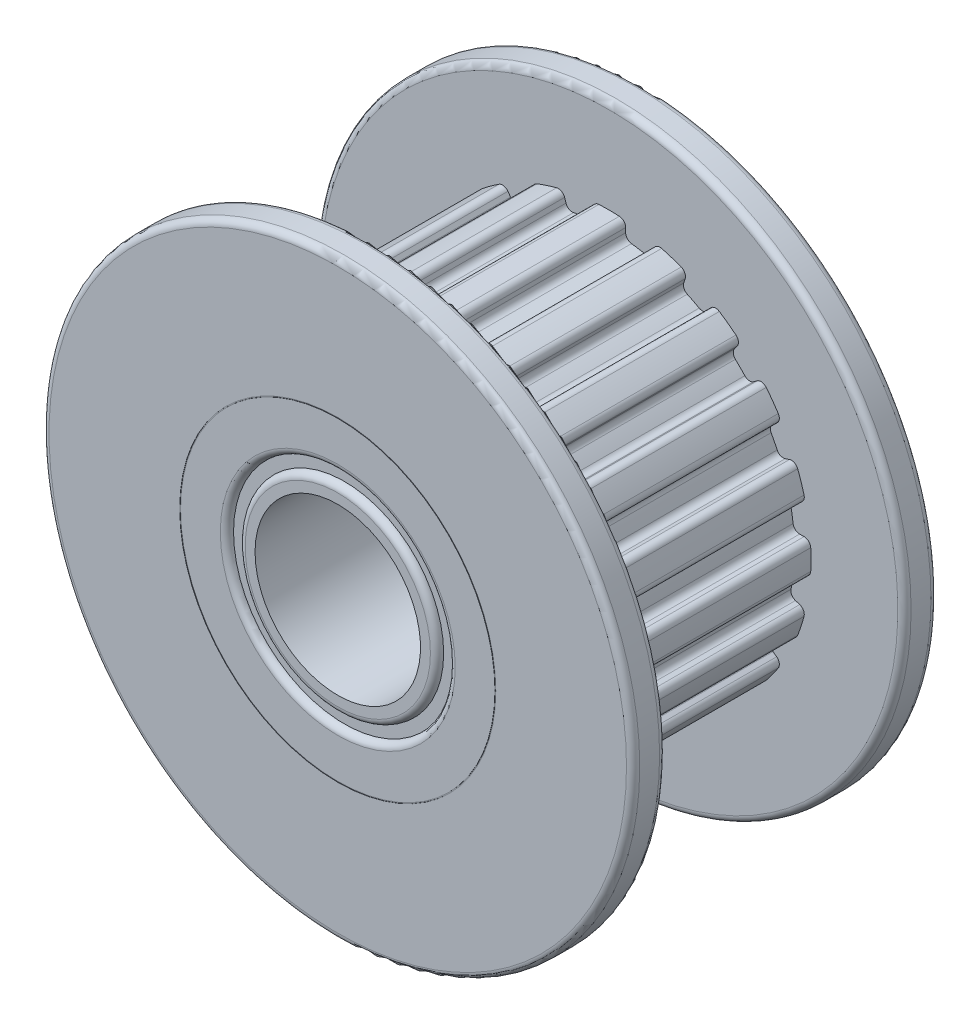
SolidWorks part; units mm, degrees
material "1060-H12 Válcovaný drát (SS)"
ref_plane "Front Plane" through (0, 0, 0) normal (0, 0, 1) x (1, 0, 0)
ref_plane "Top Plane" through (0, 0, 0) normal (0, 1, 0) x (1, 0, 0)
ref_plane "Right Plane" through (0, 0, 0) normal (1, 0, 0) x (0, 0, -1)
sketch "Skica1" plane through (0, 0, 0) normal (0, 0, 1) x (1, 0, 0)
  line L0 (0, 0) -> (0, 6.1) construction
  line L1 (0, 6.1) -> (-0.5, 6.0795) construction
  line L2 (0, 6.1) -> (0.5, 6.0795) construction
  line L3 (-0.5, 6.0795) -> (-0.5, 5.5776)
  line L4 (-0.5, 5.5776) -> (-1.2481, 5.4592) construction
  line L5 (0.5, 6.0795) -> (0.5, 5.5776)
  line L6 (1.4031, 5.9364) -> (1.2481, 5.4592)
  line L7 (2.3542, 5.6274) -> (2.1991, 5.1501)
  line L8 (3.1689, 5.2123) -> (2.8739, 4.8063)
  line L9 (3.9779, 4.6245) -> (3.683, 4.2185)
  line L10 (4.6245, 3.9779) -> (4.2185, 3.683)
  line L11 (5.2123, 3.1689) -> (4.8063, 2.8739)
  line L12 (5.6274, 2.3542) -> (5.1501, 2.1991)
  line L13 (5.9364, 1.4031) -> (5.4592, 1.2481)
  line L14 (6.0795, 0.5) -> (5.5776, 0.5)
  line L15 (6.0795, -0.5) -> (5.5776, -0.5)
  line L16 (5.9364, -1.4031) -> (5.4592, -1.2481)
  line L17 (5.6274, -2.3542) -> (5.1501, -2.1991)
  line L18 (5.2123, -3.1689) -> (4.8063, -2.8739)
  line L19 (4.6245, -3.9779) -> (4.2185, -3.683)
  line L20 (3.9779, -4.6245) -> (3.683, -4.2185)
  line L21 (3.1689, -5.2123) -> (2.8739, -4.8063)
  line L22 (2.3542, -5.6274) -> (2.1991, -5.1501)
  line L23 (1.4031, -5.9364) -> (1.2481, -5.4592)
  line L24 (0.5, -6.0795) -> (0.5, -5.5776)
  line L25 (-0.5, -6.0795) -> (-0.5, -5.5776)
  line L26 (-1.4031, -5.9364) -> (-1.2481, -5.4592)
  line L27 (-2.3542, -5.6274) -> (-2.1991, -5.1501)
  line L28 (-3.1689, -5.2123) -> (-2.8739, -4.8063)
  line L29 (-3.9779, -4.6245) -> (-3.683, -4.2185)
  line L30 (-4.6245, -3.9779) -> (-4.2185, -3.683)
  line L31 (-5.2123, -3.1689) -> (-4.8063, -2.8739)
  line L32 (-5.6274, -2.3542) -> (-5.1501, -2.1991)
  line L33 (-5.9364, -1.4031) -> (-5.4592, -1.2481)
  line L34 (-6.0795, -0.5) -> (-5.5776, -0.5)
  line L35 (-6.0795, 0.5) -> (-5.5776, 0.5)
  line L36 (-5.9364, 1.4031) -> (-5.4592, 1.2481)
  line L37 (-5.6274, 2.3542) -> (-5.1501, 2.1991)
  line L38 (-5.2123, 3.1689) -> (-4.8063, 2.8739)
  line L39 (-4.6245, 3.9779) -> (-4.2185, 3.683)
  line L40 (-3.9779, 4.6245) -> (-3.683, 4.2185)
  line L41 (-3.1689, 5.2123) -> (-2.8739, 4.8063)
  line L42 (-2.3542, 5.6274) -> (-2.1991, 5.1501)
  line L43 (-1.4031, 5.9364) -> (-1.2481, 5.4592)
  circle A0 centre (0, 0) radius 6.1 construction
  circle A1 centre (0, 0) radius 5.6 construction
  arc A2 (-1.2481, 5.4592) -> (-0.5, 5.5776) centre (0, 0) cw
  arc A3 (-0.5, 6.0795) -> (0.5, 6.0795) centre (0, 0) cw
  arc A4 (0.5, 5.5776) -> (1.2481, 5.4592) centre (0, 0) cw
  arc A5 (1.4031, 5.9364) -> (2.3542, 5.6274) centre (0, 0) cw
  arc A6 (2.1991, 5.1501) -> (2.8739, 4.8063) centre (0, 0) cw
  arc A7 (3.1689, 5.2123) -> (3.9779, 4.6245) centre (0, 0) cw
  arc A8 (3.683, 4.2185) -> (4.2185, 3.683) centre (0, 0) cw
  arc A9 (4.6245, 3.9779) -> (5.2123, 3.1689) centre (0, 0) cw
  arc A10 (4.8063, 2.8739) -> (5.1501, 2.1991) centre (0, 0) cw
  arc A11 (5.6274, 2.3542) -> (5.9364, 1.4031) centre (0, 0) cw
  arc A12 (5.4592, 1.2481) -> (5.5776, 0.5) centre (0, 0) cw
  arc A13 (6.0795, 0.5) -> (6.0795, -0.5) centre (0, 0) cw
  arc A14 (5.5776, -0.5) -> (5.4592, -1.2481) centre (0, 0) cw
  arc A15 (5.9364, -1.4031) -> (5.6274, -2.3542) centre (0, 0) cw
  arc A16 (5.1501, -2.1991) -> (4.8063, -2.8739) centre (0, 0) cw
  arc A17 (5.2123, -3.1689) -> (4.6245, -3.9779) centre (0, 0) cw
  arc A18 (4.2185, -3.683) -> (3.683, -4.2185) centre (0, 0) cw
  arc A19 (3.9779, -4.6245) -> (3.1689, -5.2123) centre (0, 0) cw
  arc A20 (2.8739, -4.8063) -> (2.1991, -5.1501) centre (0, 0) cw
  arc A21 (2.3542, -5.6274) -> (1.4031, -5.9364) centre (0, 0) cw
  arc A22 (1.2481, -5.4592) -> (0.5, -5.5776) centre (0, 0) cw
  arc A23 (0.5, -6.0795) -> (-0.5, -6.0795) centre (0, 0) cw
  arc A24 (-0.5, -5.5776) -> (-1.2481, -5.4592) centre (0, 0) cw
  arc A25 (-1.4031, -5.9364) -> (-2.3542, -5.6274) centre (0, 0) cw
  arc A26 (-2.1991, -5.1501) -> (-2.8739, -4.8063) centre (0, 0) cw
  arc A27 (-3.1689, -5.2123) -> (-3.9779, -4.6245) centre (0, 0) cw
  arc A28 (-3.683, -4.2185) -> (-4.2185, -3.683) centre (0, 0) cw
  arc A29 (-4.6245, -3.9779) -> (-5.2123, -3.1689) centre (0, 0) cw
  arc A30 (-4.8063, -2.8739) -> (-5.1501, -2.1991) centre (0, 0) cw
  arc A31 (-5.6274, -2.3542) -> (-5.9364, -1.4031) centre (0, 0) cw
  arc A32 (-5.4592, -1.2481) -> (-5.5776, -0.5) centre (0, 0) cw
  arc A33 (-6.0795, -0.5) -> (-6.0795, 0.5) centre (0, 0) cw
  arc A34 (-5.5776, 0.5) -> (-5.4592, 1.2481) centre (0, 0) cw
  arc A35 (-5.9364, 1.4031) -> (-5.6274, 2.3542) centre (0, 0) cw
  arc A36 (-5.1501, 2.1991) -> (-4.8063, 2.8739) centre (0, 0) cw
  arc A37 (-5.2123, 3.1689) -> (-4.6245, 3.9779) centre (0, 0) cw
  arc A38 (-4.2185, 3.683) -> (-3.683, 4.2185) centre (0, 0) cw
  arc A39 (-3.9779, 4.6245) -> (-3.1689, 5.2123) centre (0, 0) cw
  arc A40 (-2.8739, 4.8063) -> (-2.1991, 5.1501) centre (0, 0) cw
  arc A41 (-2.3542, 5.6274) -> (-1.4031, 5.9364) centre (0, 0) cw
  point P110 (0, 0)
  dimension "D1" = 12.2
  dimension "D2" = 0.5
  dimension "D3" = 1
  dimension "D5" = 20
extrude "Přidat vysunutím1" add sketch "Skica1" along normal blind 7.2
fillet "Zaoblit1" radius 0.2 80 edges at (-2.1991, 5.1501, 3.6) (-2.3542, 5.6274, 3.6) (-1.4031, 5.9364, 3.6) (-1.2481, 5.4592, 3.6) (-0.5, 5.5776, 3.6) (-0.5, 6.0795, 3.6) (0.5, 6.0795, 3.6) (0.5, 5.5776, 3.6) (1.2481, 5.4592, 3.6) (1.4031, 5.9364, 3.6) (2.3542, 5.6274, 3.6) (2.1991, 5.1501, 3.6) (-2.8739, 4.8063, 3.6) (-3.1689, 5.2123, 3.6) (-3.9779, 4.6245, 3.6) (-3.683, 4.2185, 3.6) (-4.2185, 3.683, 3.6) (-4.6245, 3.9779, 3.6) (-5.2123, 3.1689, 3.6) (-4.8063, 2.8739, 3.6) (-5.1501, 2.1991, 3.6) (-5.6274, 2.3542, 3.6) (-5.9364, 1.4031, 3.6) (-5.4592, 1.2481, 3.6) (-5.5776, 0.5, 3.6) (-6.0795, 0.5, 3.6) (-6.0795, -0.5, 3.6) (-5.5776, -0.5, 3.6) (-5.4592, -1.2481, 3.6) (-5.9364, -1.4031, 3.6) (-5.6274, -2.3542, 3.6) (-5.1501, -2.1991, 3.6) (-4.8063, -2.8739, 3.6) (-5.2123, -3.1689, 3.6) (-4.6245, -3.9779, 3.6) (-4.2185, -3.683, 3.6) (-3.683, -4.2185, 3.6) (-3.9779, -4.6245, 3.6) (-3.1689, -5.2123, 3.6) (-2.8739, -4.8063, 3.6) (-2.1991, -5.1501, 3.6) (-2.3542, -5.6274, 3.6) (-1.4031, -5.9364, 3.6) (-1.2481, -5.4592, 3.6) (-0.5, -5.5776, 3.6) (-0.5, -6.0795, 3.6) (0.5, -6.0795, 3.6) (0.5, -5.5776, 3.6) (1.2481, -5.4592, 3.6) (1.4031, -5.9364, 3.6) (2.3542, -5.6274, 3.6) (2.1991, -5.1501, 3.6) (2.8739, -4.8063, 3.6) (3.1689, -5.2123, 3.6) (3.9779, -4.6245, 3.6) (3.683, -4.2185, 3.6) (4.2185, -3.683, 3.6) (4.6245, -3.9779, 3.6) (5.2123, -3.1689, 3.6) (4.8063, -2.8739, 3.6) (5.1501, -2.1991, 3.6) (5.6274, -2.3542, 3.6) (5.9364, -1.4031, 3.6) (5.4592, -1.2481, 3.6) (5.5776, -0.5, 3.6) (6.0795, -0.5, 3.6) (6.0795, 0.5, 3.6) (5.5776, 0.5, 3.6) (5.4592, 1.2481, 3.6) (5.9364, 1.4031, 3.6) (5.6274, 2.3542, 3.6) (5.1501, 2.1991, 3.6) (4.8063, 2.8739, 3.6) (5.2123, 3.1689, 3.6) (4.6245, 3.9779, 3.6) (4.2185, 3.683, 3.6) (3.683, 4.2185, 3.6) (3.9779, 4.6245, 3.6) (2.8739, 4.8063, 3.6) (3.1689, 5.2123, 3.6)
sketch "Skica2" plane through (0, 0, 7.2) normal (0, 0, 1) x (1, 0, 0)
  circle A0 centre (0, 0) radius 8.925
  dimension "D1" = 17.85
extrude "Přidat vysunutím2" add sketch "Skica2" along normal blind 1
sketch "Skica3" plane through (0, 0, 0) normal (0, 0, -1) x (-1, 0, 0)
  circle A0 centre (0, 0) radius 8.925
  dimension "D1" = 17.85
extrude "Přidat vysunutím3" add sketch "Skica3" along normal blind 1
sketch "Skica4" plane through (0, 0, -1) normal (0, 0, -1) x (-1, 0, 0)
  circle A0 centre (0, 0) radius 2.5
  dimension "D1" = 5
sketch "Skica8" plane through (0, 0, 0) normal (0, 1, 0) x (1, 0, 0)
  line L0 (0, 1) -> (0, 0) construction
  line L1 (8.925, 1) -> (-8.925, 1) construction
  circle A0 centre (0, 0.5) radius 2
  point P8 (0, 0.5)
  point P10 (0, 0.5)
  dimension "D1" = 4
sketch "Skica23" plane through (0, 0, -1) normal (0, 0, -1) x (-1, 0, 0)
  circle A0 centre (0, 0) radius 2.5
  dimension "D1" = 5
extrude "Odebrat vysunutím4" cut sketch "Skica23" against normal through all
sketch "Skica25" plane through (0, 0, 8.2) normal (0, 0, 1) x (1, 0, 0)
  circle A0 centre (0, 0) radius 4.75
  circle A1 centre (0, 0) radius 4.775
  dimension "D1" = 9.5
  dimension "D2" = 9.55
extrude "Odebrat vysunutím6" cut sketch "Skica25" against normal blind 0.01
sketch "Skica27" plane through (0, 0, -1) normal (0, 0, -1) x (-1, 0, 0)
  circle A1 centre (0, 0) radius 4.775
  circle A2 centre (0, 0) radius 4.775
  circle A3 centre (0, 0) radius 4.75
  circle A4 centre (0, 0) radius 4.75
  dimension "D1" = 0
  dimension "D2" = 0
extrude "Odebrat vysunutím7" cut sketch "Skica27" against normal blind 0.01
sketch "Skica28" plane through (0, 0, 8.2) normal (0, 0, 1) x (1, 0, 0)
  circle A0 centre (0, 0) radius 3.5
  circle A1 centre (0, 0) radius 2.5
  dimension "D1" = 5
extrude "Přidat vysunutím4" add sketch "Skica28" against normal up to surface (9.2 mm away) up to face at (-4.775, 0, -1)
sketch "Skica29" plane through (0, 0, 8.2) normal (0, 0, 1) x (1, 0, 0)
  circle A0 centre (0, 0) radius 3
  circle A1 centre (0, 0) radius 3.35
  dimension "D1" = 6.7
  dimension "D2" = 6
extrude "Odebrat vysunutím8" cut sketch "Skica29" against normal blind 0.2
sketch "Skica30" plane through (0, 0, -1) normal (0, 0, -1) x (-1, 0, 0)
  circle A1 centre (0, 0) radius 3.35
  circle A2 centre (0, 0) radius 3.35
  circle A3 centre (0, 0) radius 3
  circle A4 centre (0, 0) radius 3
  dimension "D1" = 0
  dimension "D2" = 0
extrude "Odebrat vysunutím9" cut sketch "Skica30" against normal blind 0.2
fillet "Zaoblit2" radius 0.2 4 edges at (-3, 0, -1) (-3.35, 0, -1) (3, 0, 8.2) (3.35, 0, 8.2)
fillet "Zaoblit3" radius 0.2 4 edges at (8.925, 0, 8.2) (8.925, 0, 7.2) (-8.925, 0, 0) (-8.925, 0, -1)
